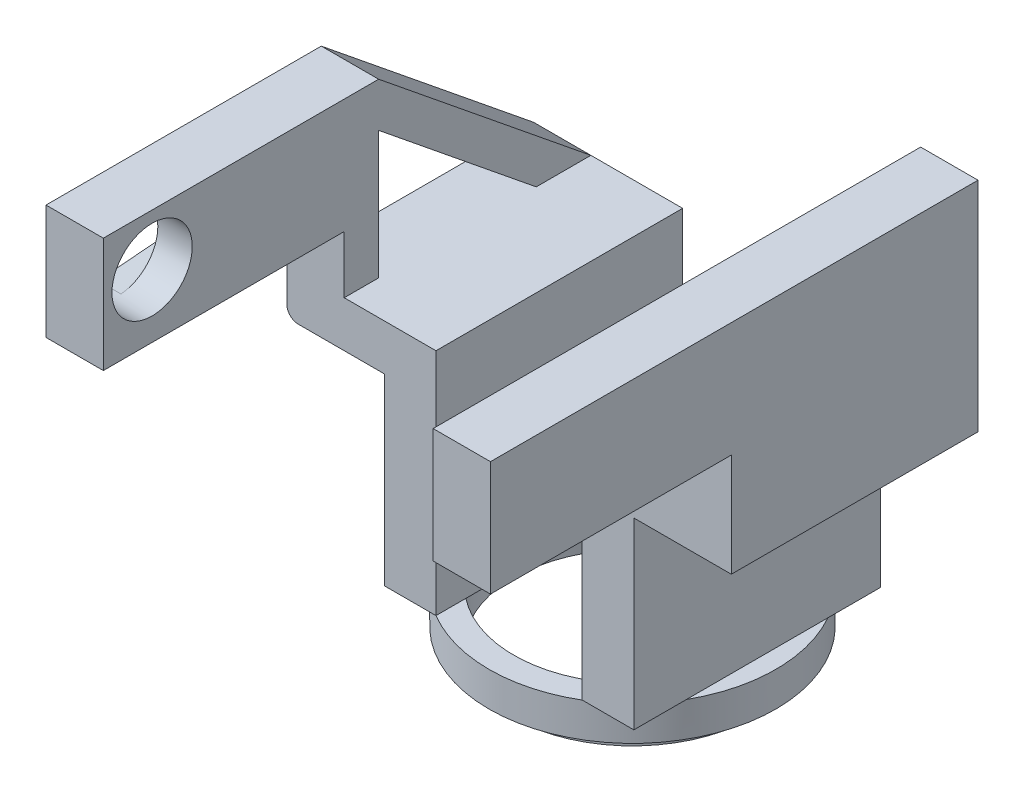
SolidWorks part; units mm, degrees
other "标注1"
sketch "草图6" plane through (-12.5, 24.5, -12.5) normal (-0.0349, 0.9206, -0.3889) x (-0.9818, -0.1042, -0.1586)
other "标注2"
sketch "草图8" plane through (12.5, 24.5, -12.5) normal (0.2759, 0.3831, -0.8815) x (-0.9572, 0.0258, -0.2884)
ref_plane "前视基准面" through (0, 0, 0) normal (0, 0, 1) x (1, 0, 0)
ref_plane "上视基准面" through (0, 0, 0) normal (0, 1, 0) x (1, 0, 0)
ref_plane "右视基准面" through (0, 0, 0) normal (1, 0, 0) x (0, 0, -1)
sketch "草图1" plane through (0, 0, 0) normal (0, 1, 0) x (1, 0, 0)
  circle A0 centre (0, 0) radius 10.35
  circle A1 centre (0, 0) radius 10.65
  dimension "D1" = 20.7
  dimension "D2" = 21.3
extrude "凸台-拉伸1" add sketch "草图1" along normal blind 1.5
ref_plane "基准面1" through (0, 1.5, 0) normal (0, 1, 0) x (1, 0, 0)
sketch "草图2" plane through (0, 1.5, 0) normal (0, 1, 0) x (1, 0, 0)
  circle A1 centre (0, 0) radius 12.5
  circle A2 centre (0, 0) radius 10.35
  circle A3 centre (0, 0) radius 10.35 construction
  dimension "D1" = 25
extrude "凸台-拉伸2" add sketch "草图2" along normal blind 3
ref_plane "基准面2" through (0, 4.5, 0) normal (0, 1, 0) x (1, 0, 0)
sketch "草图3" plane through (0, 4.5, 0) normal (0, 1, 0) x (1, 0, 0)
  line L0 (0, 5.6293) -> (0, -6.3899) construction
  line L1 (-5.2673, 0) -> (4.6454, 0) construction
  line L3 (-6.375, 15.9) -> (6.375, 15.9) construction
  line L4 (-6.375, 15.9) -> (-6.375, -15.9) construction
  line L5 (-6.375, -15.9) -> (6.375, -15.9) construction
  line L6 (6.375, 15.9) -> (6.375, -15.9) construction
  line L7 (6.375, 10.7522) -> (10.875, 10.7522)
  line L8 (6.375, 10.7522) -> (6.375, -10.7522)
  line L9 (6.375, -10.7522) -> (10.875, -10.7522)
  line L10 (10.875, 10.7522) -> (10.875, -10.7522)
  line L11 (-10.875, 10.7522) -> (-6.375, 10.7522)
  line L12 (-10.875, 10.7522) -> (-10.875, -10.7522)
  line L13 (-10.875, -10.7522) -> (-6.375, -10.7522)
  line L14 (-6.375, 10.7522) -> (-6.375, -10.7522)
  circle A1 centre (0, 0) radius 12.5 construction
  point P17 (-6.375, 10.7522)
  point P18 (-6.375, -10.7522)
  point P22 (6.375, 10.7522)
  point P23 (6.375, -10.7522)
  point P26 (6.375, -10.7522)
  dimension "D1" = 31.8
  dimension "D2" = 12.75
  dimension "D3" = 4.5
extrude "凸台-拉伸3" add sketch "草图3" along normal blind 20
ref_plane "基准面4" through (0, 1.5, 0) normal (0, -1, 0) x (-1, 0, 0)
sketch "草图5" plane through (0, 1.5, 0) normal (0, -1, 0) x (-1, 0, 0)
  circle A0 centre (0, 0) radius 12.5
  arc A2 (6.375, -10.7522) -> (-6.375, -10.7522) centre (0, 0) ccw construction
extrude "切除-拉伸3" cut sketch "草图5" against normal blind 23 flip side to cut
ref_plane "基准面5" through (-6.375, 0, 0) normal (1, 0, 0) x (0, 0, -1)
sketch "草图7" plane through (-6.375, 0, 0) normal (1, 0, 0) x (0, 0, -1)
  line L1 (-10.7522, 24.5) -> (10.7522, 24.5)
  line L2 (-10.7522, 24.5) -> (-10.7522, 20.5)
  line L3 (-10.7522, 20.5) -> (10.7522, 20.5)
  line L4 (10.7522, 24.5) -> (10.7522, 20.5)
  dimension "D1" = 4
extrude "凸台-拉伸5" add sketch "草图7" against normal blind 13
ref_plane "基准面6" through (0, 24.5, 0) normal (0, 1, 0) x (1, 0, 0)
sketch "草图9" plane through (0, 24.5, 0) normal (0, 1, 0) x (1, 0, 0)
  line L1 (-19.375, 10.7522) -> (-14.375, 10.7522)
  line L2 (-19.375, 10.7522) -> (-19.375, -10.7522)
  line L3 (-19.375, -10.7522) -> (-14.375, -10.7522)
  line L4 (-14.375, 10.7522) -> (-14.375, -10.7522)
  dimension "D1" = 5
extrude "凸台-拉伸6" add sketch "草图9" along normal blind 15
ref_plane "基准面7" through (-19.375, 0, 0) normal (-1, 0, 0) x (0, 0, 1)
sketch "草图10" plane through (-19.375, 0, 0) normal (-1, 0, 0) x (0, 0, 1)
  line L0 (-10.7522, 24.5) -> (7.7522, 39.5)
  line L1 (7.7522, 39.5) -> (-10.7522, 39.5)
  line L2 (-10.7522, 39.5) -> (-10.7522, 24.5)
  line L3 (7.7522, 35.6381) -> (-5.9881, 24.5)
  line L4 (7.15, 24.5) -> (-7.15, 24.5) construction
  line L5 (-5.9881, 24.5) -> (7.7522, 24.5)
  line L6 (7.7522, 24.5) -> (7.7522, 35.6381)
  line L7 (10.7522, 39.5) -> (10.7522, 20.5) construction
  dimension "D1" = 3
  dimension "D2" = 4
  dimension "D3" = 3
  dimension "D4" = 3
extrude "切除-拉伸4" cut sketch "草图10" against normal blind 12
fillet "圆角4" radius 1 1 edges at (-19.375, 20.5, 0)
ref_plane "基准面8" through (0, 0, 10.7522) normal (0, 0, 1) x (1, 0, 0)
sketch "草图11" plane through (0, 0, 10.7522) normal (0, 0, 1) x (1, 0, 0)
  line L1 (-19.375, 39.5) -> (-14.375, 39.5)
  line L2 (-19.375, 39.5) -> (-19.375, 29.5)
  line L3 (-19.375, 29.5) -> (-14.375, 29.5)
  line L4 (-14.375, 39.5) -> (-14.375, 29.5)
  dimension "D1" = 10
extrude "凸台-拉伸7" add sketch "草图11" along normal blind 21
ref_plane "基准面9" through (-19.375, 0, 0) normal (-1, 0, 0) x (0, 0, 1)
sketch "草图12" plane through (-19.375, 0, 0) normal (-1, 0, 0) x (0, 0, 1)
  line L0 (10.3292, 37.0929) -> (27.2139, 38.4881)
  line L1 (10.3292, 32.9071) -> (27.2139, 31.5119)
  line L2 (31.7522, 39.5) -> (31.7522, 29.5) construction
  line L3 (7.7522, 39.5) -> (31.7522, 39.5) construction
  circle A0 centre (27.5022, 35) radius 3.5
  circle A1 centre (10.5022, 35) radius 2.1
  dimension "D1" = 7
  dimension "D2" = 4.2
  dimension "D4" = 4.25
  dimension "D3" = 17
  dimension "D5" = 4.5
extrude "切除-拉伸9" cut sketch "草图12" against normal blind 5 contours A0
extrude "切除-拉伸10" cut sketch "草图12<10>" against normal blind 2 contours A1 L1 A0 L0 | A1 region at (-19.375, 35, 18.7912) region at (-19.375, 35, 10.5022)
sketch "草图12<10>" plane through (-19.375, 0, 0) normal (-1, 0, 0) x (0, 0, 1) same geometry as "草图12"
ref_plane "基准面10" through (0, 0, 0) normal (1, 0, 0) x (0, 0, -1)
mirror "镜向1" about plane through (0, 0, 0) normal (1, 0, 0) of "凸台-拉伸7", "凸台-拉伸3", "凸台-拉伸6", "凸台-拉伸5"
ref_plane "基准面11" through (14.375, 0, 0) normal (-1, 0, 0) x (0, 0, 1)
sketch "草图13" plane through (14.375, 0, 0) normal (-1, 0, 0) x (0, 0, 1)
  circle A0 centre (27.5022, 35) radius 2.5
  circle A1 centre (27.5022, 35) radius 3.5 construction
  dimension "D1" = 5
extrude "切除-拉伸11" cut sketch "草图13" against normal blind 3
